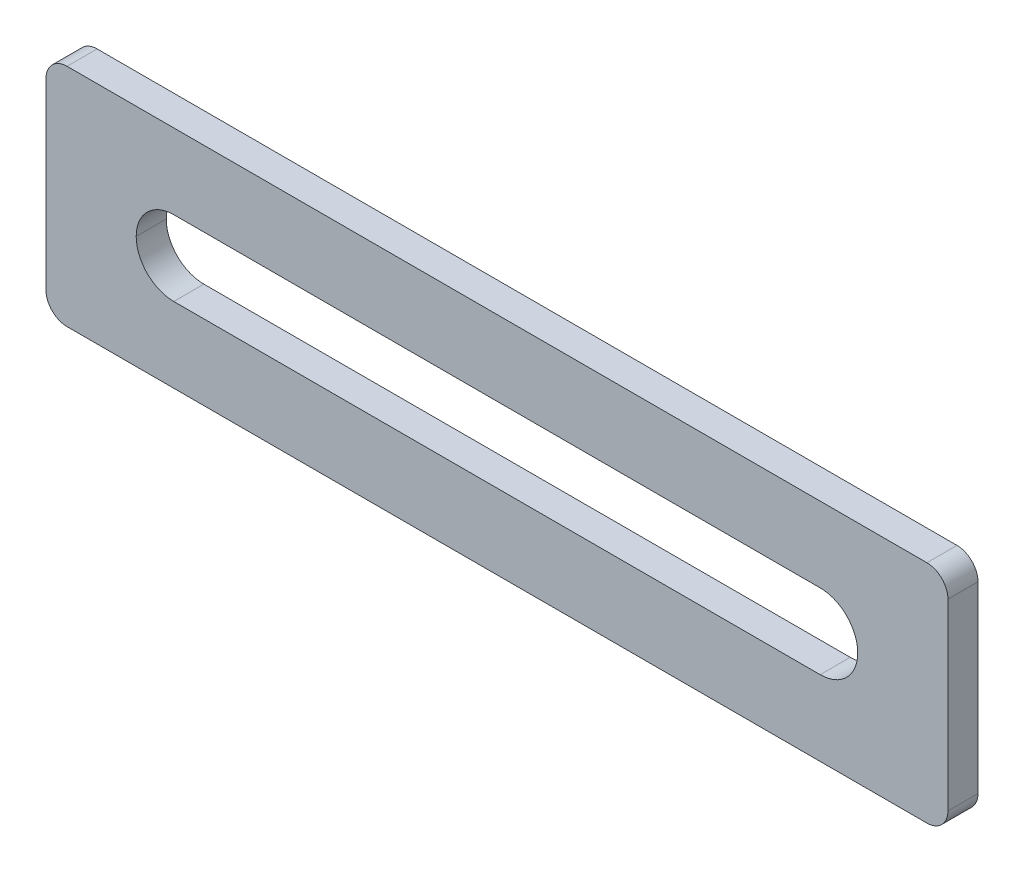
SolidWorks part; units mm, degrees
ref_plane "Front Plane" through (0, 0, 0) normal (0, 0, 1) x (1, 0, 0)
ref_plane "Top Plane" through (0, 0, 0) normal (0, 1, 0) x (1, 0, 0)
ref_plane "Right Plane" through (0, 0, 0) normal (1, 0, 0) x (0, 0, -1)
sketch "Sketch1" plane through (0, 0, 0) normal (0, 0, 1) x (1, 0, 0)
  line L1 (0, 0) -> (76.2, 0)
  line L2 (0, 0) -> (0, 19.05)
  line L3 (0, 19.05) -> (76.2, 19.05)
  line L4 (76.2, 0) -> (76.2, 19.05)
extrude "Boss-Extrude1" add sketch "Sketch1" along normal blind 2.54
sketch "Sketch2" plane through (0, 0, 2.54) normal (0, 0, 1) x (1, 0, 0)
  line L1 (7.62, 6.35) -> (68.58, 6.35)
  line L2 (7.62, 6.35) -> (7.62, 12.7)
  line L3 (7.62, 12.7) -> (68.58, 12.7)
  line L4 (68.58, 6.35) -> (68.58, 12.7)
extrude "Cut-Extrude1" cut sketch "Sketch2" against normal blind 2.54
fillet "Fillet1" radius 3.175 4 edges at (68.58, 6.35, 1.27) (7.62, 12.7, 1.27) (7.62, 6.35, 1.27) (68.58, 12.7, 1.27)
fillet "Fillet2" radius 1.778 4 edges at (0, 19.05, 1.27) (0, 0, 1.27) (76.2, 0, 1.27) (76.2, 19.05, 1.27)
